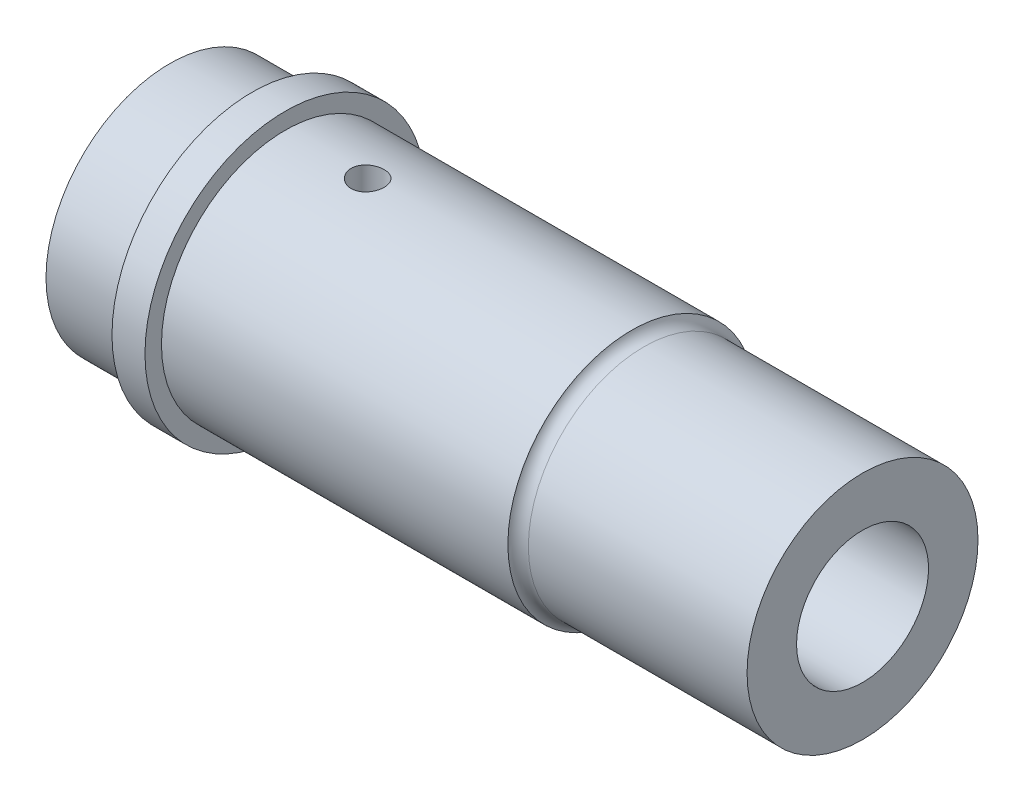
SolidWorks part; units mm, degrees
material "Plain Carbon Steel"
ref_plane "Front Plane" through (0, 0, 0) normal (0, 0, 1) x (1, 0, 0)
ref_plane "Top Plane" through (0, 0, 0) normal (0, 1, 0) x (1, 0, 0)
ref_plane "Right Plane" through (0, 0, 0) normal (1, 0, 0) x (0, 0, -1)
sketch "Sketch1" plane through (0, 0, 0) normal (1, 0, 0) x (0, 0, -1)
  circle A0 centre (0, 0) radius 7.5
  dimension "D1" = 15
extrude "Boss-Extrude1" add sketch "Sketch1" along normal blind 5
sketch "Sketch2" plane through (5, 0, 0) normal (1, 0, 0) x (0, 0, -1)
  circle A0 centre (0, 0) radius 8.5
  dimension "D1" = 17
extrude "Boss-Extrude2" add sketch "Sketch2" along normal blind 2
sketch "Sketch3" plane through (7, 0, 0) normal (1, 0, 0) x (0, 0, -1)
  circle A0 centre (0, 0) radius 7.5
  dimension "D1" = 15
extrude "Boss-Extrude3" add sketch "Sketch3" along normal blind 35
sketch "Sketch4" plane through (0, 0, 0) normal (-1, 0, 0) x (0, 0, 1)
  circle A0 centre (0, 0) radius 4
  dimension "D1" = 8
extrude "Cut-Extrude1" cut sketch "Sketch4" against normal through all
ref_plane "Plane1" through (0, 7.5, 0) normal (0, 1, 0) x (1, 0, 0)
sketch "Sketch7" plane through (0, 7.5, 0) normal (0, 1, 0) x (1, 0, 0)
  line L0 (-2.75, 0) -> (2.75, 0) construction
  line L1 (0, -8.25) -> (0, 8.25) construction
  line L2 (7, -7.5) -> (7, 7.5) construction
  circle A0 centre (12, 0) radius 1
  dimension "D1" = 2
  dimension "D2" = 12
extrude "Cut-Extrude3" cut sketch "Sketch7" against normal up to next
sketch "Sketch9" plane through (42, 0, 0) normal (1, 0, 0) x (0, 0, -1)
  circle A0 centre (0, 0) radius 7.5
  circle A1 centre (0, 0) radius 7
  dimension "D1" = 15
  dimension "D2" = 14
extrude "Cut-Extrude6" cut sketch "Sketch9" against normal blind 14
fillet "Fillet1" radius 0.8 1 edges at (28, 0, -7)
sketch "Sketch10" plane through (0, 0, 0) normal (-1, 0, 0) x (0, 0, 1)
  line L1 (-1.5, 2.5) -> (1.5, 2.5)
  line L2 (-1.5, 2.5) -> (-1.5, 5.5)
  line L3 (-1.5, 5.5) -> (1.5, 5.5)
  line L4 (1.5, 2.5) -> (1.5, 5.5)
  line L5 (-1.5, 2.5) -> (1.5, 5.5) construction
  line L6 (-1.5, 5.5) -> (1.5, 2.5) construction
  circle A0 centre (0, 0) radius 4 construction
  point P0 (0, 4)
  dimension "D1" = 3
  dimension "D2" = 3
extrude "Cut-Extrude7" cut sketch "Sketch10" against normal blind 28
ref_plane "Plane2" through (27, 0, 0) normal (1, 0, 0) x (0, 0, -1)
sketch "Sketch12" plane through (27, 0, 0) normal (1, 0, 0) x (0, 0, -1)
  line L1 (-2.5, -10) -> (2.5, -10)
  line L2 (-2.5, -10) -> (-2.5, -5)
  line L3 (-2.5, -5) -> (2.5, -5)
  line L4 (2.5, -10) -> (2.5, -5)
  line L5 (-2.5, -10) -> (2.5, -5) construction
  line L6 (-2.5, -5) -> (2.5, -10) construction
  circle A0 centre (0, 0) radius 7.5 construction
  circle A1 centre (0, 0) radius 7.5 construction
  point P0 (0, -7.5)
  dimension "D1" = 5
  dimension "D2" = 5
extrude "Cut-Extrude8" cut sketch "Sketch12" against normal offset from surface (18.5 mm away) 1.5 up to face at (7, 0, -7.5)
